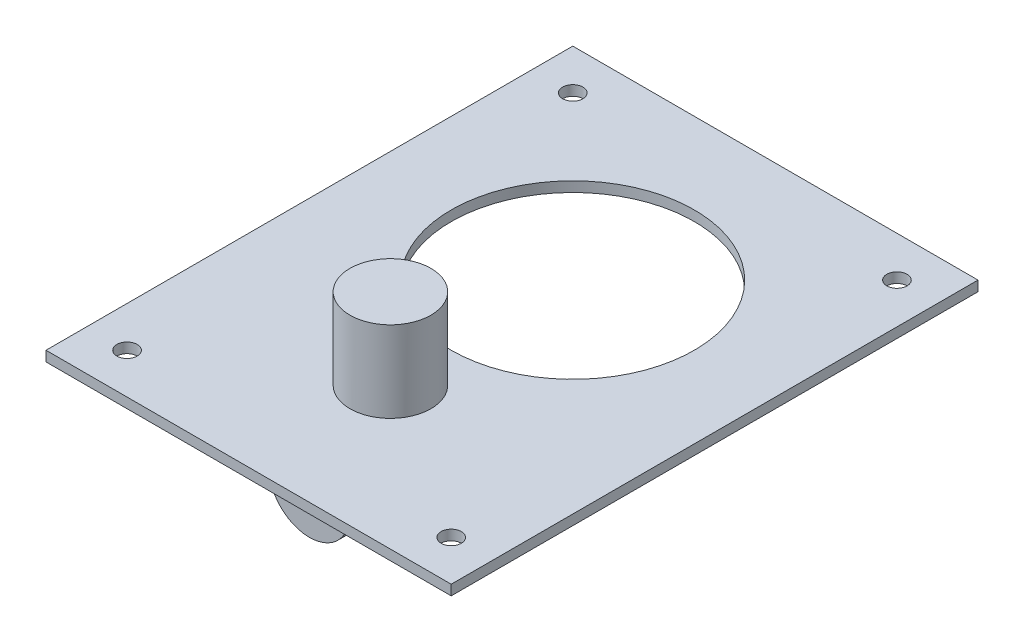
SolidWorks part; units mm, degrees
ref_plane "Front Plane" through (0, 0, 0) normal (0, 0, 1) x (1, 0, 0)
ref_plane "Top Plane" through (0, 0, 0) normal (0, 1, 0) x (1, 0, 0)
ref_plane "Right Plane" through (0, 0, 0) normal (1, 0, 0) x (0, 0, -1)
sketch "Sketch1" plane through (0, 0, 0) normal (0, 1, 0) x (1, 0, 0)
  line L1 (-127, -127) -> (127, -127) construction
  line L2 (-127, -127) -> (-127, 127)
  line L3 (-127, 127) -> (127, 127)
  line L4 (127, -127) -> (127, 127)
  line L5 (-127, -127) -> (127, 127) construction
  line L6 (-127, 127) -> (127, -127) construction
  line L7 (-127, -127) -> (127, -127) construction
  line L8 (-127, -127) -> (-127, -203.2)
  line L9 (-127, -203.2) -> (127, -203.2)
  line L10 (127, -127) -> (127, -203.2)
  circle A0 centre (0, 0) radius 76.2
  point P0 (0, 0)
  dimension "D1" = 152.4
  dimension "D2" = 254
  dimension "D3" = 76.2
extrude "Boss-Extrude1" add sketch "Sketch1" along normal mid plane 6.35
ref_axis "Axis1" through (0, 3.175, 0) along (0, -1, 0)
sketch "Sketch2" plane through (0, 3.175, 0) normal (0, 1, 0) x (1, 0, 0)
  circle A0 centre (0, -114.3) radius 25.4
  dimension "D1" = 50.8
  dimension "D2" = 114.3
extrude "Boss-Extrude2" add sketch "Sketch2" along normal blind 50.8 contours A0
sketch "Sketch3" plane through (0, 3.175, 0) normal (0, 1, 0) x (1, 0, 0)
  line L0 (-101.6, 101.6) -> (-101.6, 127) construction
  line L1 (127, 127) -> (-127, 127) construction
  line L2 (-101.6, 101.6) -> (-127, 101.6) construction
  line L3 (-127, 127) -> (-127, -203.2) construction
  line L4 (-101.6, -203.2) -> (-101.6, -177.8) construction
  line L5 (-127, -203.2) -> (127, -203.2) construction
  line L6 (-101.6, -177.8) -> (-127, -177.8) construction
  circle A0 centre (-101.6, 101.6) radius 6.35
  circle A1 centre (-101.6, -177.8) radius 6.35
  dimension "D1" = 12.7
  dimension "D2" = 25.4
extrude "Cut-Extrude1" cut sketch "Sketch3" against normal through all
mirror "Mirror1" about plane through (0, 0, 0) normal (1, 0, 0) of "Cut-Extrude1"
sketch "Sketch4" plane through (0, 0, 0) normal (0, 0, 1) x (1, 0, 0)
  line L0 (-127, -3.175) -> (127, -3.175) construction
  circle A0 centre (0, -28.575) radius 25.4
  point P2 (0, 0)
  dimension "D1" = 50.8
extrude "Boss-Extrude3" add sketch "Sketch4" along normal blind 50.8 from offset 114.3 separate body
